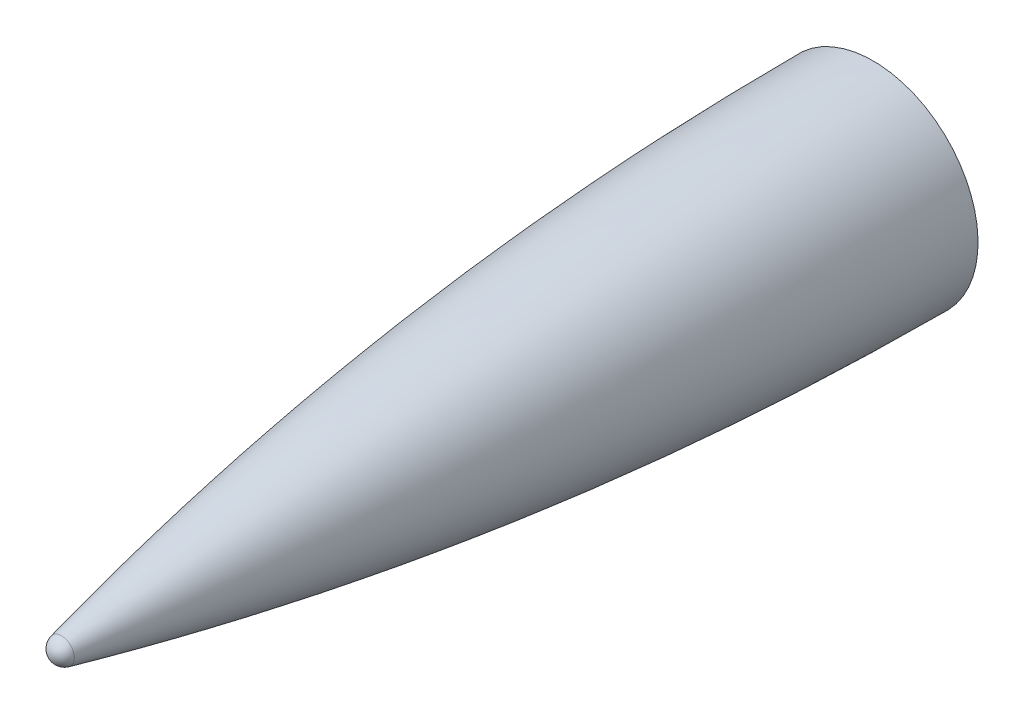
SolidWorks part; units mm, degrees
ref_plane "Front Plane" through (0, 0, 0) normal (0, 0, 1) x (1, 0, 0)
ref_plane "Top Plane" through (0, 0, 0) normal (0, 1, 0) x (1, 0, 0)
ref_plane "Right Plane" through (0, 0, 0) normal (1, 0, 0) x (0, 0, -1)
sketch "Unblunted Reference" plane through (0, 0, 0) normal (1, 0, 0) x (0, 0, -1)
  line L2 (0, 0) -> (-561.5876, 0) construction
  line L3 (0, 0) -> (0, 50.8) construction
  arc A1 (-385.322, 0) -> (-398.022, 0) centre (-391.672, 0) ccw construction
  spline S0 degree 4 poles (-459.753, -10.5198) (-458.8979, -10.2876) (-457.188, -9.8245) (-454.6259, -9.1341) (-451.1978, -8.2181) (-446.9606, -7.0946) (-442.7021, -5.9783) (-438.5157, -4.8918) (-434.2469, -3.7972) (-430.9886, -2.9671) (-427.3742, -2.0565) (-424.5079, -1.3371) (-420.2908, -0.2927) (-418.3417, 0.1872) (-415.2679, 0.939) (-413.1135, 1.4623) (-411.0374, 1.964) (-408.2622, 2.6314) (-404.3783, 3.5579) (-400.1738, 4.5483) (-395.9226, 5.5377) (-391.6512, 6.5217) (-387.341, 7.5045) (-382.3125, 8.6363) (-375.1216, 10.2294) (-366.485, 12.1023) (-357.8374, 13.9269) (-349.1801, 15.7031) (-341.959, 17.1509) (-336.1783, 18.2897) (-330.3938, 19.4091) (-324.6056, 20.5091) (-317.3658, 21.8597) (-305.7724, 23.9689) (-269.4922, 30.276) (-211.1797, 38.8064) (-152.5404, 44.8505) (-95.1967, 48.4336) (-62.816, 49.6937) (-52.5106, 50.0254) (-43.676, 50.2603) (-37.7858, 50.3971) (-32.6315, 50.4995) (-28.2133, 50.5749) (-24.5472, 50.6293) (-21.6333, 50.6676) (-18.7349, 50.7009) (-15.8532, 50.7294) (-12.9736, 50.753) (-10.0727, 50.772) (-7.2352, 50.7862) (-4.3734, 50.7957) (-0.7824, 50.8006) (1.2225, 50.8003) (5.5599, 50.7937) (8.5094, 50.78) (12.2323, 50.7594) (15.5816, 50.7319) (19.1128, 50.6975) (22.5547, 50.6563) (26.0564, 50.608) (29.5522, 50.5525) (33.0747, 50.4897) (36.6075, 50.4195) (39.2594, 50.3614) (41.0265, 50.3204) (41.9099, 50.2993) knots 0 0 0 0 0 0.006985 0.01397 0.020955 0.02794 0.041657 0.048516 0.055375 0.062233 0.069092 0.075951 0.08281 0.088494 0.094178 0.09702 0.099862 0.105546 0.116914 0.128282 0.134092 0.139901 0.151519 0.163138 0.174757 0.197994 0.221231 0.23285 0.244468 0.256087 0.267706 0.279324 0.290943 0.31418 0.360654 0.569789 0.755687 0.778924 0.81378 0.825399 0.837017 0.848636 0.860254 0.866064 0.871873 0.877557 0.883241 0.888925 0.894609 0.900293 0.905978 0.911662 0.917346 0.924192 0.931037 0.937883 0.944729 0.951575 0.958421 0.965267 0.972113 0.979084 0.986056 0.993028 1 1 1 1 1 construction
  spline S1 degree 4 poles (-419.1, 0) (-418.516, 0.1437) (-417.3411, 0.432) (-415.2679, 0.939) (-413.1135, 1.4623) (-411.0374, 1.964) (-408.2622, 2.6314) (-404.3783, 3.5579) (-400.1738, 4.5483) (-395.9226, 5.5377) (-391.6512, 6.5217) (-387.341, 7.5045) (-382.3125, 8.6363) (-375.1216, 10.2294) (-366.485, 12.1023) (-357.8374, 13.9269) (-349.1801, 15.7031) (-341.959, 17.1509) (-336.1783, 18.2897) (-330.3938, 19.4091) (-324.6056, 20.5091) (-317.3658, 21.8597) (-305.7724, 23.9689) (-269.4922, 30.276) (-211.1797, 38.8064) (-152.5404, 44.8505) (-95.1967, 48.4336) (-62.816, 49.6937) (-52.5106, 50.0254) (-43.676, 50.2603) (-37.7858, 50.3971) (-32.6315, 50.4995) (-28.2133, 50.5749) (-24.5472, 50.6293) (-21.6333, 50.6676) (-18.7349, 50.7009) (-15.8532, 50.7294) (-12.9736, 50.753) (-10.0727, 50.772) (-7.2352, 50.7862) (-4.3734, 50.7957) (-1.8111, 50.7992) (-0.6014, 50.8) (0, 50.8) knots 0.08281 0.08281 0.08281 0.08281 0.08281 0.088494 0.094178 0.09702 0.099862 0.105546 0.116914 0.128282 0.134092 0.139901 0.151519 0.163138 0.174757 0.197994 0.221231 0.23285 0.244468 0.256087 0.267706 0.279324 0.290943 0.31418 0.360654 0.569789 0.755687 0.778924 0.81378 0.825399 0.837017 0.848636 0.860254 0.866064 0.871873 0.877557 0.883241 0.888925 0.894609 0.900293 0.905978 0.911662 0.917346 0.917346 0.917346 0.917346 0.917346
  point P5 (0, 0)
  point P8 (-393.0949, 6.1885)
  dimension "D2" = 6.35
  dimension "D1" = 50.8
sketch "Sketch2" plane through (0, 0, 0) normal (1, 0, 0) x (0, 0, -1)
  line L0 (0, 0) -> (0, 50.8)
  line L1 (0, 0) -> (-461.8494, 0) construction
  line L2 (-419.1, 20.3837) -> (-419.1, -20.3837) construction
  line L3 (-398.022, 0) -> (0, 0)
  arc A0 (-393.095, 6.1885) -> (-398.022, 0) centre (-391.672, 0) ccw
  arc A1 (-385.322, 0) -> (-393.095, 6.1885) centre (-391.672, 0) ccw construction
  spline S0 degree 4 poles (-431.6185, -3.1289) (-431.0154, -2.9758) (-429.8036, -2.6689) (-427.3957, -2.0611) (-423.7557, -1.1502) (-419.543, -0.1058) (-414.6866, 1.0826) (-409.917, 2.2364) (-405.6376, 3.2578) (-402.1583, 4.0809) (-398.9748, 4.8262) (-396.945, 5.3) (-393.8534, 6.0144) (-392.403, 6.3479) (-388.822, 7.1672) (-385.7644, 7.8589) (-381.5113, 8.814) (-375.8789, 10.0602) (-370.0306, 11.3344) (-364.3088, 12.5578) (-357.3562, 14.0196) (-350.4386, 15.4474) (-343.4871, 16.8503) (-336.5479, 18.2179) (-330.7521, 19.3389) (-326.1173, 20.2222) (-317.9989, 21.747) (-306.3911, 23.8625) (-293.603, 26.0866) (-279.6319, 28.3875) (-265.6445, 30.5882) (-251.6417, 32.6885) (-237.6204, 34.6631) (-223.5821, 36.5119) (-209.531, 38.2599) (-193.1237, 40.1815) (-176.6964, 41.9265) (-160.2514, 43.4946) (-146.1445, 44.7122) (-134.3834, 45.6636) (-122.6157, 46.5306) (-110.8421, 47.3132) (-96.7075, 48.1508) (-84.9239, 48.7643) (-73.1361, 49.2933) (-62.5242, 49.6932) (-55.4482, 49.9281) (-49.5514, 50.1027) (-44.8326, 50.2296) (-38.9361, 50.3725) (-33.0349, 50.4942) (-27.1405, 50.5947) (-21.8248, 50.6661) (-18.2956, 50.7058) (-15.3271, 50.7336) (-13.005, 50.7526) (-10.5727, 50.7685) (-8.3406, 50.7812) (-5.7598, 50.7907) (-3.7878, 50.7971) (-0.6994, 50.8003) (0.7749, 50.8003) (4.5572, 50.796) (7.7549, 50.7841) (12.323, 50.7603) (17.0436, 50.7194) (22.0649, 50.6646) (26.9213, 50.5958) (31.2978, 50.5233) (34.6635, 50.4583) (37.1532, 50.407) (38.3807, 50.3801) (38.9996, 50.3664) (39.3098, 50.3595) knots 0 0 0 0 0 0.005242 0.010484 0.020968 0.031452 0.041936 0.052295 0.062653 0.067832 0.073012 0.078191 0.08337 0.088334 0.093298 0.103226 0.113154 0.123081 0.142937 0.152865 0.162793 0.182648 0.202504 0.212432 0.22236 0.232287 0.242215 0.281927 0.321638 0.341494 0.361349 0.401061 0.440772 0.460627 0.480483 0.520194 0.579761 0.599617 0.619473 0.639328 0.67904 0.698895 0.718751 0.758462 0.778318 0.798174 0.808101 0.818029 0.827957 0.837885 0.857741 0.867668 0.877596 0.88256 0.887524 0.892488 0.897452 0.902416 0.90738 0.912344 0.917307 0.922444 0.927581 0.937855 0.948128 0.958402 0.968801 0.979201 0.9896 0.9948 0.9974 1 1 1 1 1 construction
  spline S1 degree 4 poles (-393.095, 6.1885) (-392.6155, 6.2988) (-391.6621, 6.5174) (-388.822, 7.1672) (-385.7644, 7.8589) (-381.5113, 8.814) (-375.8789, 10.0602) (-370.0306, 11.3344) (-364.3088, 12.5578) (-357.3562, 14.0196) (-350.4386, 15.4474) (-343.4871, 16.8503) (-336.5479, 18.2179) (-330.7521, 19.3389) (-326.1173, 20.2222) (-317.9989, 21.747) (-306.3911, 23.8625) (-293.603, 26.0866) (-279.6319, 28.3875) (-265.6445, 30.5882) (-251.6417, 32.6885) (-237.6204, 34.6631) (-223.5821, 36.5119) (-209.531, 38.2599) (-193.1237, 40.1815) (-176.6964, 41.9265) (-160.2514, 43.4946) (-146.1445, 44.7122) (-134.3834, 45.6636) (-122.6157, 46.5306) (-110.8421, 47.3132) (-96.7075, 48.1508) (-84.9239, 48.7643) (-73.1361, 49.2933) (-62.5242, 49.6932) (-55.4482, 49.9281) (-49.5514, 50.1027) (-44.8326, 50.2296) (-38.9361, 50.3725) (-33.0349, 50.4942) (-27.1405, 50.5947) (-21.8248, 50.6661) (-18.2956, 50.7058) (-15.3271, 50.7336) (-13.005, 50.7526) (-10.5727, 50.7685) (-8.3406, 50.7812) (-5.7598, 50.7907) (-3.7878, 50.7971) (-1.4915, 50.7995) (-0.492, 50.8) (0, 50.8) knots 0.08337 0.08337 0.08337 0.08337 0.08337 0.088334 0.093298 0.103226 0.113154 0.123081 0.142937 0.152865 0.162793 0.182648 0.202504 0.212432 0.22236 0.232287 0.242215 0.281927 0.321638 0.341494 0.361349 0.401061 0.440772 0.460627 0.480483 0.520194 0.579761 0.599617 0.619473 0.639328 0.67904 0.698895 0.718751 0.758462 0.778318 0.798174 0.808101 0.818029 0.827957 0.837885 0.857741 0.867668 0.877596 0.88256 0.887524 0.892488 0.897452 0.902416 0.90738 0.912344 0.917307 0.917307 0.917307 0.917307 0.917307
  point P8 (-419.1, 0)
  point P9 (-393.095, 6.1885)
  dimension "D1" = 50.8
  dimension "D5" = 6.35
  dimension "D2" = 419.1
  dimension "D3" = 26.005
  dimension "D4" = 6.1885
  dimension "D6" = 27.428
revolve "Revolve3" add sketch "Sketch2" angle 360 about L3
equation "\"R\"= 2'base radius"
equation "\"L\"= 16.5'overall length"
equation "\"rho\"= ( \"R\" ^ 2 + \"L\" ^ 2 ) / ( 2 * \"R\" )'ogive radius"
equation "\"rn\"= 0.25'spherical cap radius"
equation "\"xo\"= \"L\" - sqr ( ( \"rho\" - \"rn\" ) ^ 2 - ( \"rho\" - \"R\" ) ^ 2 )'spherical cap center (from origin)"
equation "\"yt\"= \"rn\" * ( \"rho\" - \"R\" ) / ( \"rho\" - \"rn\" )'tangency y-coordinate"
equation "\"xt\"= \"xo\" - sqr ( ( \"rn\" ^ 2 ) - ( \"yt\" ^ 2 ) )'tangency x-coordinate"
equation "\"xa\"= \"xo\" - \"rn\"'apex location (from origin)"
equation "\"D1@Unblunted Reference\" = \"R\""
equation "\"D2@Unblunted Reference\" = \"rn\""
equation "\"D1@Sketch2\"=\"R\""
equation "\"D2@Sketch2\"=\"L\""
equation "\"D3@Sketch2\"=\"xt\""
equation "\"D4@Sketch2\"=\"yt\""
equation "\"D5@Sketch2\"=\"rn\""
equation "\"D6@Sketch2\"=\"xo\""
